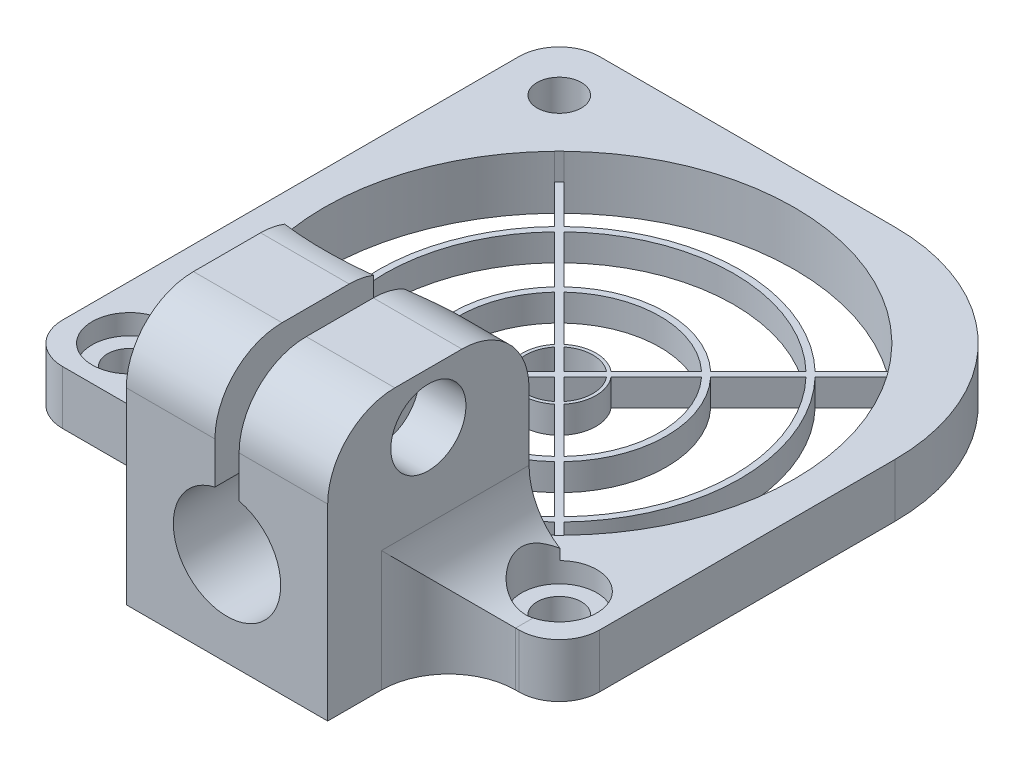
SolidWorks part; units mm, degrees
ref_plane "Alzado" through (0, 0, 0) normal (0, 0, 1) x (1, 0, 0)
ref_plane "Planta" through (0, 0, 0) normal (0, 1, 0) x (1, 0, 0)
ref_plane "Vista lateral" through (0, 0, 0) normal (1, 0, 0) x (0, 0, -1)
sketch "Croquis1" plane through (0, 0, 0) normal (0, 1, 0) x (1, 0, 0)
  line L1 (0, 0) -> (40, 0)
  line L2 (0, 0) -> (0, 40)
  line L3 (0, 40) -> (40, 40)
  line L4 (40, 0) -> (40, 40)
  line L5 (4, 36) -> (36, 36) construction
  line L6 (4, 36) -> (4, 4) construction
  line L7 (4, 4) -> (36, 4) construction
  line L8 (36, 36) -> (36, 4) construction
  circle A0 centre (4, 36) radius 1.65
  circle A1 centre (4, 4) radius 1.65
  circle A2 centre (36, 4) radius 1.65
  dimension "D7" = 3.3
  dimension "D1" = 40
  dimension "D2" = 40
  dimension "D3" = 32
  dimension "D4" = 32
  dimension "D5" = 4
  dimension "D6" = 4
extrude "Saliente-Extruir1" add sketch "Croquis1" along normal blind 2
sketch "Croquis2" plane through (0, 2, 0) normal (0, 1, 0) x (1, 0, 0)
  line L0 (40, 0) -> (40, 40) construction
  line L1 (31.75, 6) -> (16.75, 6)
  line L2 (31.75, 6) -> (31.75, -9)
  line L3 (31.75, -9) -> (16.75, -9)
  line L4 (16.75, 6) -> (16.75, -9)
  line L5 (40, 40) -> (0, 40) construction
  dimension "D1" = 15
  dimension "D2" = 15
  dimension "D3" = 8.25
  dimension "D4" = 34
extrude "Saliente-Extruir2" add sketch "Croquis2" along normal blind 17
sketch "Croquis3" plane through (0, 0, -6) normal (0, 0, -1) x (-1, 0, 0)
  line L0 (-31.75, 19) -> (-31.75, 2) construction
  line L1 (-31.75, 2) -> (-16.75, 2) construction
  circle A0 centre (-24.25, 7) radius 4
  dimension "D1" = 8
  dimension "D2" = 7.5
  dimension "D3" = 5
extrude "Cortar-Extruir1" cut sketch "Croquis3" against normal through all and the other way through all
sketch "Croquis4" plane through (31.75, 0, 0) normal (1, 0, 0) x (0, 0, -1)
  line L0 (-1.5, 19) -> (-1.5, 2) construction
  line L1 (-9, 19) -> (6, 19) construction
  line L2 (-9, 2) -> (0, 2) construction
  circle A0 centre (-1.5, 15.2) radius 1.6
  dimension "D1" = 3.2
  dimension "D2" = 3.8
extrude "Cortar-Extruir2" cut sketch "Croquis4" against normal up to surface (15 mm away) up to face at (16.75, 8.8, 1.2)
sketch "Croquis5" plane through (31.75, 0, 0) normal (1, 0, 0) x (0, 0, -1)
  circle A0 centre (-1.5, 15.2) radius 2.8
  dimension "D1" = 5.6
extrude "Cortar-Extruir3" cut sketch "Croquis5" against normal blind 3.5
sketch "Croquis6" plane through (16.75, 0, 0) normal (-1, 0, 0) x (0, 0, 1)
  line L1 (-1.8486, 15.2) -> (-0.1743, 12.3)
  line L2 (-0.1743, 12.3) -> (3.1743, 12.3)
  line L3 (3.1743, 12.3) -> (4.8486, 15.2)
  line L4 (4.8486, 15.2) -> (3.1743, 18.1)
  line L5 (3.1743, 18.1) -> (-0.1743, 18.1)
  line L6 (-0.1743, 18.1) -> (-1.8486, 15.2)
  line L7 (-6, 19) -> (9, 19) construction
  circle A0 centre (1.5, 15.2) radius 2.9 construction
  dimension "D1" = 5.8
extrude "Cortar-Extruir4" cut sketch "Croquis6" against normal blind 4
sketch "Croquis7" plane through (0, 0, -6) normal (0, 0, -1) x (-1, 0, 0)
  line L0 (-24.25, 2) -> (-24.25, 19) construction
  line L1 (-31.75, 2) -> (-16.75, 2) construction
  line L2 (-31.75, 19) -> (-16.75, 19) construction
  line L4 (-23.35, 9) -> (-25.15, 9)
  line L5 (-23.35, 9) -> (-23.35, 19)
  line L6 (-23.35, 19) -> (-25.15, 19)
  line L7 (-25.15, 9) -> (-25.15, 19)
  dimension "D1" = 1.8
  dimension "D2" = 0.9
  dimension "D3" = 10
extrude "Cortar-Extruir5" cut sketch "Croquis7" against normal up to surface (15 mm away) up to face at (20.25, 7, 9)
sketch "Croquis8" plane through (0, 2, 0) normal (0, -1, 0) x (1, 0, 0)
  line L4 (16.75, 9) -> (16.75, 0)
  line L5 (16.75, 0) -> (31.75, 0)
  line L6 (31.75, 0) -> (31.75, 9)
  line L7 (31.75, 9) -> (16.75, 9)
  line L8 (16.75, 9) -> (16.75, 0)
  line L9 (16.75, 0) -> (31.75, 0)
  line L10 (31.75, 0) -> (31.75, 9)
  line L11 (31.75, 9) -> (16.75, 9)
  dimension "D1" = 0
extrude "Saliente-Extruir3" add sketch "Croquis8" along normal up to surface (2 mm away) up to face at (4, 0, -2.35)
sketch "Croquis9" plane through (0, 2, 0) normal (0, 1, 0) x (1, 0, 0)
  line L1 (31.75, 6) -> (40, 6)
  line L2 (31.75, 6) -> (31.75, 0)
  line L3 (31.75, 0) -> (40, 0)
  line L4 (40, 6) -> (40, 0)
  line L5 (16.75, 6) -> (0, 6)
  line L6 (16.75, 6) -> (16.75, 0)
  line L7 (16.75, 0) -> (0, 0)
  line L8 (0, 6) -> (0, 0)
  line L9 (0, 40) -> (6, 40)
  line L10 (0, 40) -> (0, 6)
  line L11 (0, 6) -> (6, 6)
  line L12 (6, 40) -> (6, 6)
  circle A0 centre (4, 4) radius 1.65 construction
  circle A1 centre (4, 4) radius 1.65
  circle A2 centre (36, 4) radius 1.65 construction
  circle A3 centre (36, 4) radius 1.65
  circle A4 centre (4, 36) radius 1.65 construction
  circle A5 centre (4, 36) radius 1.65
  circle M14 centre (36, 4) radius 1.65
  circle M15 centre (4, 4) radius 1.65
  circle M16 centre (4, 36) radius 1.65
  line M17 (31.75, 6) -> (31.75, 0)
  line M18 (31.75, 0) -> (40, 0)
  line M19 (40, 0) -> (40, 40)
  line M20 (40, 40) -> (0, 40)
  line M21 (0, 40) -> (0, 0)
  line M22 (0, 0) -> (16.75, 0)
  line M23 (16.75, 0) -> (16.75, 6)
  dimension "D1" = 6
extrude "Saliente-Extruir4" add sketch "Croquis9" along normal blind 2 contours L12 L5 M20 M21 M16 | L5 M23 M21 M22 M15 | L1 M17 M18 M19 M14 region at (2.9562, 2, -22.4311) region at (35.875, 2, -5.898) region at (8.782, 2, -2.907)
fillet "Redondeo1" radius 15 1 edges at (40, 1, -40)
fillet "Redondeo2" radius 5 4 edges at (20.05, 19, 9) (28.45, 19, 9) (20.05, 19, -6) (28.45, 19, -6)
fillet "Redondeo3" radius 3 3 edges at (0, 2, -40) (0, 2, 0) (40, 2, 0)
fillet "Redondeo4" radius 5 4 edges at (31.75, 4, -3) (16.75, 4, -3) (16.75, 2, 0) (31.75, 2, 0)
sketch "Croquis12" plane through (0, 0, 0) normal (0, -1, 0) x (1, 0, 0)
  line L0 (4, -36) -> (36, -4) construction
  line L1 (4, -4) -> (35.6066, -35.6066) construction
  line L2 (32.8965, -7.4429) -> (7.4429, -32.8965)
  line L3 (7.1035, -32.5571) -> (32.5571, -7.1035)
  line L4 (32.5571, -32.8965) -> (7.1035, -7.4429)
  line L5 (32.8965, -32.5571) -> (7.4429, -7.1035)
  circle A0 centre (20, -20) radius 18
  arc A1 (25, -40) -> (40, -25) centre (25, -25) ccw construction
  circle A2 centre (20, -20) radius 2.5
  circle A3 centre (20, -20) radius 2.74
  circle A4 centre (20, -20) radius 7.5
  circle A5 centre (20, -20) radius 13
  circle A6 centre (20, -20) radius 13.48
  circle A7 centre (20, -20) radius 7.98
  circle A8 centre (20, -20) radius 17.52
  dimension "D1" = 36
  dimension "D9" = 5
  dimension "D10" = 5.48
  dimension "D11" = 15
  dimension "D12" = 26
  dimension "D13" = 26.96
  dimension "D14" = 15.96
  dimension "D15" = 35.04
  dimension "D2" = 0.24
  dimension "D3" = 0.24
  dimension "D4" = 0.24
  dimension "D5" = 0.24
  dimension "D6" = 0.24
  dimension "D7" = 0.24
  dimension "D8" = 0.24
extrude "Cortar-Extruir8" cut sketch "Croquis12" against normal through all contours L5 A8 L2 A6 | L2 A8 L4 A6 | A7 L2 A5 L4 | A7 L4 A5 L3 | A7 L5 A5 L2 | L5 A4 L2 A3 | L2 A4 L4 A3 | L4 A4 L3 A3 | L3 A4 L5 A3 | L4 A2 L3 | L2 A2 L4 | L5 A2 L2 | L3 A2 L5 | A7 L3 A5 L5 | L3 A8 L5 A6 | L4 A8 L3 A6 region at (34.094, 0, -20) region at (20, 0, -5.906) region at (29.6883, 0, -20) region at (20, 0, -10.3117) region at (20, 0, -34.094) region at (5.906, 0, -20) region at (25.0203, 0, -20) region at (20, 0, -14.9797) region at (20, 0, -29.6883) region at (10.3117, 0, -20) region at (21.6497, 0, -20) region at (20, 0, -18.3503) region at (20, 0, -25.0203) region at (14.9797, 0, -20) region at (20, 0, -21.6497) region at (18.3503, 0, -20)
sketch "Croquis13" plane through (0, 2, 0) normal (0, 1, 0) x (1, 0, 0)
  line L0 (6, 9.4667) -> (6, 6) construction
  line L1 (6, 9.4667) -> (6, 6)
  line L2 (9.4667, 6) -> (6, 6) construction
  line L3 (9.4667, 6) -> (6, 6)
  line L4 (7.4429, 7.7824) -> (7.7824, 7.4429)
  arc A0 (6, 9.4667) -> (7.4429, 7.7824) centre (20, 20) ccw construction
  arc A1 (6, 9.4667) -> (7.4429, 7.7824) centre (20, 20) ccw
  arc A2 (7.7824, 7.4429) -> (9.4667, 6) centre (20, 20) ccw construction
  arc A3 (7.7824, 7.4429) -> (9.4667, 6) centre (20, 20) ccw
extrude "Saliente-Extruir5" add sketch "Croquis13" along normal up to surface (2 mm away) up to face at (5.2887, 4, -16.0454)
sketch "Croquis14" plane through (0, 2, 0) normal (0, 1, 0) x (1, 0, 0)
  line L0 (25, 40) -> (6, 40) construction
  line L1 (25, 40) -> (6, 40)
  line L2 (6, 40) -> (6, 30.5333) construction
  line L3 (6, 40) -> (6, 30.5333)
  line L4 (40, 6) -> (40, 25) construction
  line L5 (40, 6) -> (40, 25)
  line L6 (40, 6) -> (30.5333, 6) construction
  line L7 (40, 6) -> (30.5333, 6)
  line L8 (32.2176, 7.4429) -> (32.5571, 7.7824)
  line L9 (32.2176, 32.5571) -> (32.5571, 32.2176)
  line L10 (7.4429, 32.2176) -> (7.7824, 32.5571)
  arc A0 (32.2176, 32.5571) -> (7.7824, 32.5571) centre (20, 20) ccw construction
  arc A1 (32.2176, 32.5571) -> (7.7824, 32.5571) centre (20, 20) ccw
  arc A2 (32.5571, 7.7824) -> (32.5571, 32.2176) centre (20, 20) ccw construction
  arc A3 (32.5571, 7.7824) -> (32.5571, 32.2176) centre (20, 20) ccw
  arc A4 (40, 25) -> (25, 40) centre (25, 25) ccw construction
  arc A5 (40, 25) -> (25, 40) centre (25, 25) ccw
  arc A6 (30.5333, 6) -> (32.2176, 7.4429) centre (20, 20) ccw construction
  arc A7 (30.5333, 6) -> (32.2176, 7.4429) centre (20, 20) ccw
  arc A8 (7.4429, 32.2176) -> (6, 30.5333) centre (20, 20) ccw construction
  arc A9 (7.4429, 32.2176) -> (6, 30.5333) centre (20, 20) ccw
extrude "Saliente-Extruir6" add sketch "Croquis14" along normal up to surface (2 mm away) up to face at (5.1174, 4, -16.9896)
sketch "Croquis15" plane through (0, 4, 0) normal (0, 1, 0) x (1, 0, 0)
  circle A0 centre (4, 4) radius 2.8
  circle A1 centre (36, 4) radius 2.8
  dimension "D1" = 5.6
  dimension "D2" = 5.6
extrude "Cortar-Extruir9" cut sketch "Croquis15" against normal blind 1.5 and the other way through all
